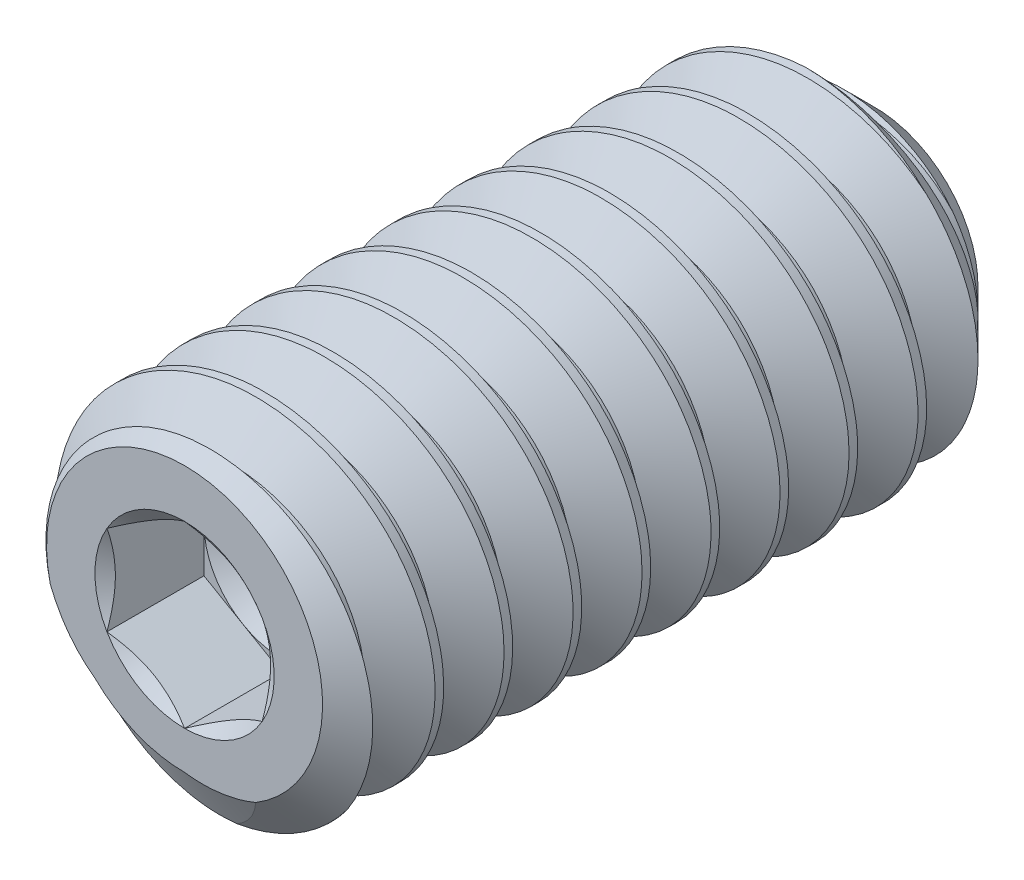
SolidWorks part; units mm, degrees
ref_plane "Front" through (0, 0, 0) normal (0, 0, 1) x (1, 0, 0)
ref_plane "Top" through (0, 0, 0) normal (0, 1, 0) x (1, 0, 0)
ref_plane "Right" through (0, 0, 0) normal (1, 0, 0) x (0, 0, -1)
sketch "Sketch22" plane through (0, 0, 0) normal (1, 0, 0) x (0, 0, -1)
  line L0 (-2, 0) -> (-2, 0.8)
  line L1 (-2, 0.8) -> (-1.86, 1)
  line L2 (-1.86, 1) -> (1.6, 1)
  line L3 (1.6, 1) -> (2, 0.6)
  line L4 (-0.13, 1) -> (-0.13, -1) construction
  line L5 (2, 0) -> (-2, 0)
  line L6 (-2, 0.8) -> (-2, -0.8) construction
  line L7 (2, 0) -> (2, 0.6)
  point P11 (-0.13, 0)
  dimension "Length" = 4
  dimension "D3" = 35
  dimension "D6" = 45
  dimension "Dia" = 2
  dimension "D1" = 1.6
  dimension "D2" = 0.4
revolve "Revolve1" add sketch "Sketch22" angle 360 about L5
ref_plane "Plane1" through (0, 0, -2) normal (0, 0, 1) x (1, 0, 0)
sketch "Sketch23" plane through (0, 0, 2) normal (0, 0, 1) x (1, 0, 0)
  line L1 (0, 0.5196) -> (-0.45, 0.2598)
  line L2 (-0.45, 0.2598) -> (-0.45, -0.2598)
  line L3 (-0.45, -0.2598) -> (0, -0.5196)
  line L4 (0, -0.5196) -> (0.45, -0.2598)
  line L5 (0.45, -0.2598) -> (0.45, 0.2598)
  line L6 (0.45, 0.2598) -> (0, 0.5196)
  circle A0 centre (0, 0) radius 0.45 construction
  dimension "Hex" = 0.9
extrude "Cut-Extrude10" cut sketch "Sketch23" against normal blind 0.5625
sketch "Sketch24" plane through (0, 0, 2) normal (0, 0, 1) x (1, 0, 0)
  circle A0 centre (0, 0) radius 0.5196
extrude "Cut-Extrude11" cut sketch "Sketch24" against normal through all draft 55
sketch "Sketch26" plane through (0, 0, 1.4375) normal (0, 0, 1) x (1, 0, 0)
  circle A0 centre (0, 0) radius 0.45 construction
  circle A1 centre (0, 0) radius 0.45
extrude "Cut-Extrude12" cut sketch "Sketch26" against normal through all draft 60
sketch "Sketch30" plane through (0, 0, 0) normal (1, 0, 0) x (0, 0, -1)
  line L0 (-1.86, 1) -> (1.6, 1) construction
  line L1 (-2, 0) -> (-2, 0.8) construction
  line L2 (2, 0) -> (2, 0.6) construction
  point P0 (-2, 1)
  point P1 (2, 1)
  point P2 (2, -1)
  point P11 (1, -1)
  dimension "D1" = 1
sketch "Sketch27" plane through (0, 0, -2) normal (0, 0, 1) x (1, 0, 0)
  circle A0 centre (0, 0) radius 1 construction
  circle A1 centre (0, 0) radius 1
curve "Helix/Spiral1" pitch 0.4 height 4.4 radius 1 centre (0, 0, -2) axis (0, 0, 1) start towards (0, 1, 0)
sketch "Sketch28" plane through (0, 0, 0) normal (1, 0, 0) x (0, 0, -1)
  line L0 (2, 1) -> (2.35, 1)
  line L1 (2.35, 1) -> (2.2, 0.7402)
  line L2 (2.2, 0.7402) -> (2.15, 0.7402)
  line L3 (2.15, 0.7402) -> (2, 1)
  line L4 (2.075, 0.8701) -> (2.275, 0.8701) construction
  line L6 (-1.86, 1) -> (1.6, 1) construction
  dimension "D1" = 0.05
  dimension "D3" = 60
  dimension "D2" = 0.2
sweep "Cut-Sweep2" cut profiles "Sketch28" path "Helix/Spiral1"
ref_plane "Contact Plane 1" through (0, 0, 2) normal (0, 0, 1) x (1, 0, 0)
ref_plane "Contact Plane 2" through (0, 0, -2) normal (0, 0, -1) x (-1, 0, 0)
ref_axis "Center Axis 1" through (0, 0, -2) along (0, 0, 1)
equation "\"D1@Sketch28\" = \"D4@Helix/Spiral1\" * .125"
equation "\"D2@Sketch28\" = \"D4@Helix/Spiral1\" * .5"
equation "\"D3@Helix/Spiral1\" = \"Length@Sketch22\" + \"D4@Helix/Spiral1\""
equation "\"D1@Sketch30\" = \"D4@Helix/Spiral1\" * 2.5"
equation "\"hex Depth@Cut-Extrude10\" = \"Hex@Sketch23\" * .625"
equation "\"D1@Sketch22\" = \"Dia@Sketch22\" * .8"
equation "\"D2@Sketch22\" = \"D4@Helix/Spiral1\""
